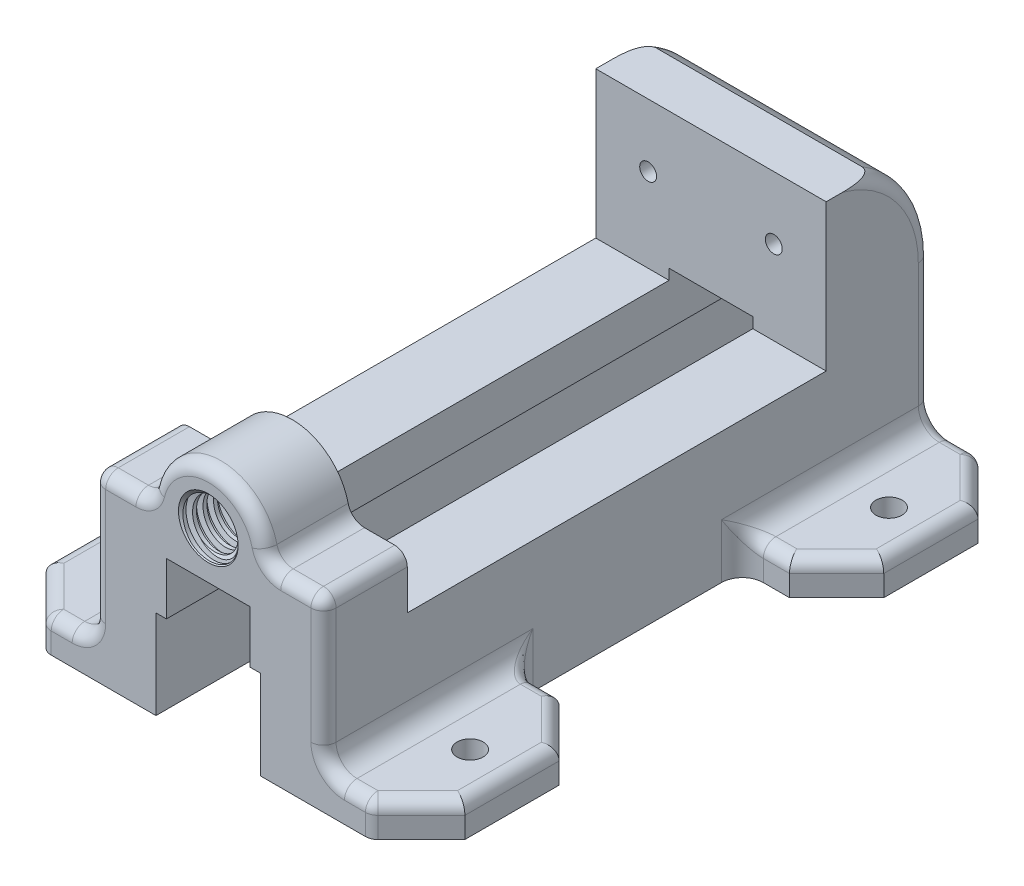
SolidWorks part; units mm, degrees
ref_plane "Front Plane" through (0, 0, 0) normal (0, 0, 1) x (1, 0, 0)
ref_plane "Top Plane" through (0, 0, 0) normal (0, 1, 0) x (1, 0, 0)
ref_plane "Right Plane" through (0, 0, 0) normal (1, 0, 0) x (0, 0, -1)
sketch "Sketch2" plane through (0, 0, 0) normal (0, 0, 1) x (1, 0, 0)
  line L1 (-34.925, 0) -> (34.925, 0)
  line L2 (-34.925, 0) -> (-34.925, 39.6748)
  line L3 (-34.925, 39.6748) -> (34.925, 39.6748)
  line L4 (34.925, 0) -> (34.925, 39.6748)
  dimension "D1" = 69.85
  dimension "D2" = 39.6748
extrude "Boss-Extrude1" add sketch "Sketch2" along normal mid plane 184.15
sketch "Sketch3" plane through (-34.925, 0, 0) normal (-1, 0, 0) x (0, 0, 1)
  line L0 (-92.075, 39.6748) -> (-60.325, 39.6748)
  line L1 (92.075, 39.6748) -> (-92.075, 39.6748) construction
  line L2 (-60.325, 39.6748) -> (-60.325, 84.1248)
  line L3 (-60.325, 84.1248) -> (-74.9527, 84.1248)
  line L4 (-92.075, 54.0779) -> (-92.075, 39.6748)
  arc A0 (-74.9527, 84.1248) -> (-92.075, 54.0779) centre (-57.15, 54.0779) ccw
  dimension "D3" = 34.925
  dimension "D1" = 31.75
  dimension "D2" = 44.45
extrude "Boss-Extrude2" add sketch "Sketch3" against normal up to surface (69.85 mm away) up to face at (34.925, 19.8374, 0)
sketch "Sketch4" plane through (0, 0, 92.075) normal (0, 0, 1) x (1, 0, 0)
  line L0 (0, 0) -> (0, 57.15) construction
  line L1 (34.925, 39.6748) -> (34.925, 55.5498)
  line L2 (34.925, 84.1248) -> (34.925, 39.6748) construction
  line L3 (34.925, 55.5498) -> (17.4498, 55.5498)
  line L4 (-17.4498, 55.5498) -> (-34.925, 55.5498)
  line L5 (-34.925, 39.6748) -> (-34.925, 84.1248) construction
  line L6 (-34.925, 55.5498) -> (-34.925, 39.6748)
  line L7 (-34.925, 39.6748) -> (34.925, 39.6748)
  arc A0 (17.4498, 55.5498) -> (-17.4498, 55.5498) centre (0, 55.5498) ccw
  dimension "D1" = 17.4498
  dimension "D2" = 55.5498
extrude "Boss-Extrude3" add sketch "Sketch4" against normal offset from surface (25.4 mm away) 127 up to face at (0, 61.8998, -60.325)
sketch "Sketch6" plane through (0, 0, 0) normal (0, -1, 0) x (1, 0, 0)
  line L0 (-49.2125, -34.925) -> (-63.5, -49.2125)
  line L1 (-34.925, -92.075) -> (-49.2125, -92.075)
  line L2 (-34.925, -92.075) -> (-34.925, -34.925)
  line L3 (-34.925, -34.925) -> (-49.2125, -34.925)
  line L4 (-63.5, -77.7875) -> (-63.5, -49.2125)
  line L5 (-49.2125, -92.075) -> (-63.5, -77.7875)
  line L6 (0, 0) -> (-25.1626, 0) construction
  line L7 (-25.1626, 0) -> (0, 0) construction
  line L8 (0, 0) -> (0, -81.2732) construction
  line L9 (-34.925, -63.5) -> (0, -63.5) construction
  circle A0 centre (-50.8, -63.5) radius 3.9624
  dimension "D1" = 7.9248
  dimension "D2" = 50.8
  dimension "D3" = 63.5
extrude "Boss-Extrude4" add sketch "Sketch6" against normal blind 10.16
mirror "Mirror4" about plane through (0, 0, 0) normal (1, 0, 0) of "Boss-Extrude4"
mirror "Mirror5" about plane through (0, 0, 0) normal (0, 0, 1) of "Boss-Extrude4", "Mirror4"
sketch "Sketch10" plane through (0, 0, 92.075) normal (0, 0, 1) x (1, 0, 0)
  line L0 (0, 0) -> (0, 42.8625) construction
  line L1 (-15.875, 0) -> (15.875, 0)
  line L2 (-49.2125, 0) -> (49.2125, 0) construction
  line L3 (15.875, 0) -> (15.875, 26.9748)
  line L4 (15.875, 26.9748) -> (12.7, 26.9748)
  line L5 (12.7, 26.9748) -> (12.7, 42.8625)
  line L6 (12.7, 42.8625) -> (-12.7, 42.8625)
  line L7 (-12.7, 42.8625) -> (-12.7, 26.9748)
  line L8 (-12.7, 26.9748) -> (-15.875, 26.9748)
  line L9 (-15.875, 26.9748) -> (-15.875, 0)
  dimension "D1" = 31.75
  dimension "D2" = 25.4
  dimension "D3" = 42.8625
  dimension "D4" = 26.9748
extrude "Cut-Extrude1" cut sketch "Sketch10" against normal through all
sketch "Sketch14" plane through (0, 0, -60.325) normal (0, 0, 1) x (1, 0, 0)
  line L0 (0, 0) -> (0, 80.9276) construction
hole_wizard "1/4-20 Tapped Hole2" positions "Sketch15" profile "Sketch16" tap size "1/4-20" standard "ANSI Inch"
sketch "Sketch15" plane through (0, 0, -60.325) normal (0, 0, 1) x (1, 0, 0)
  line L0 (0, 0) -> (0, 80.9276) construction
  line L1 (-12.7, 39.6748) -> (-34.925, 39.6748) construction
  line L2 (0, -46.2686) -> (0, 46.2686) construction
  point P0 (-19.05, 65.0748)
  point P8 (19.05, 65.0748)
  dimension "D1" = 19.05
  dimension "D2" = 25.4
sketch "Sketch16" plane through (-19.05, 65.0748, -60.325) normal (1, 0, 0) x (0, -1, 0)
  line L0 (0, 0) -> (0, 17.5358)
  line L1 (0, 17.5358) -> (2.5527, 16.002)
  line L2 (2.5527, 16.002) -> (2.5527, 0)
  line L5 (2.5527, 0) -> (0, 0)
  line L10 (0, 17.5358) -> (-2.5527, 16.002) construction
  line L11 (0, -6.35) -> (0, 107.95) construction
  dimension "Tap Drill Dia." = 5.1054
  dimension "Tap Drill Depth" = 16.002
  dimension "Drill Angle" = 118
cosmetic thread "Hole Thread2" parameters "D1"=12.7, "D2"=6.35
cosmetic thread "Hole Thread3" parameters "D1"=12.7, "D2"=6.35
sketch "Sketch18" plane through (0, 0, 92.075) normal (0, 0, 1) x (1, 0, 0)
  line L2 (-17.4498, 55.5498) -> (17.4498, 55.5498) construction
  circle A1 centre (0, 57.15) radius 7.1438
  dimension "D1" = 14.2875
  dimension "D2" = 57.15
extrude "Cut-Extrude2" cut sketch "Sketch18" against normal up to next
chamfer "Chamfer1" distance 1.905 angle 45 2 edges at (7.1438, 57.15, 66.675) (7.1438, 57.15, 92.075)
sketch "Sketch19" plane through (0, 0, 92.075) normal (0, 0, 1) x (1, 0, 0)
  circle A0 centre (0, 57.15) radius 7.1438 construction
  circle A1 centre (0, 57.15) radius 7.1438
curve "Helix/Spiral1" pitch 3.175 height 102.235 radius 7.1438 centre (0, 57.15, 92.075) axis (0, 0, -1) start towards (0, 1, 0)
sketch "Sketch20" plane through (0, 0, 0) normal (1, 0, 0) x (0, 0, -1)
  line L0 (-93.671, 65.8813) -> (-92.4856, 65.8813)
  line L1 (-92.4856, 65.8813) -> (-92.075, 64.2938)
  line L2 (-92.075, 64.2938) -> (-94.0816, 64.2938)
  line L3 (-94.0816, 64.2938) -> (-93.671, 65.8813)
  line L4 (-93.0783, 65.8813) -> (-93.0783, 64.2938) construction
  dimension "D1" = 1.5875
  dimension "D2" = 2.0066
  dimension "D3" = 29
sweep "Cut-Sweep1" cut profiles "Sketch20" path "Helix/Spiral1" align with end faces yes
fillet "Fillet1" radius 5.08 2 edges at (-17.4498, 55.5498, 79.375) (17.4498, 55.5498, 79.375)
fillet "Fillet2" radius 6.35 4 edges at (-34.925, 10.16, -63.5) (34.925, 10.16, -63.5) (34.925, 10.16, 63.5) (-34.925, 10.16, 63.5)
fillet "Fillet3" radius 6.35 4 edges at (34.925, 8.255, -34.925) (34.925, 8.255, 34.925) (-34.925, 8.255, 34.925) (-34.925, 8.255, -34.925)
fillet "Fillet5" radius 3.81 5 edges at (28.4373, 55.5498, 92.075) (18.7883, 56.6533, 92.075) (-28.4373, 55.5498, 92.075) (-18.7883, 56.6533, 92.075) (0, 72.9996, 92.075)
fillet "Fillet6" radius 3.81 10 edges at (-34.925, 55.5498, 77.47) (-34.925, 54.4339, 90.9591) (-45.2437, 10.16, 92.075) (-36.7849, 12.0199, 92.075) (45.2437, 10.16, 92.075) (36.7849, 12.0199, 92.075) (34.925, 55.5498, 77.47) (34.925, 54.4339, 90.9591) (-34.925, 34.1249, 92.075) (34.925, 34.1249, 92.075)
fillet "Fillet7" radius 3.81 8 edges at (-34.925, 71.3694, -87.494) (-45.2437, 10.16, -92.075) (-36.7849, 12.0199, -92.075) (45.2437, 10.16, -92.075) (36.7849, 12.0199, -92.075) (34.925, 71.3694, -87.494) (-34.925, 35.2939, -92.075) (34.925, 35.2939, -92.075)
fillet "Fillet8" radius 3.81 28 edges at (-49.2125, 3.175, -92.075) (-50.3284, 9.0441, -90.9591) (-45.2437, 10.16, -34.925) (-45.2437, 10.16, 34.925) (-58.2613, 10.16, 83.0263) (-50.3284, 9.0441, 90.9591) (49.2125, 3.175, -92.075) (50.3284, 9.0441, -90.9591) (36.7849, 12.0199, -33.0651) (36.7849, 12.0199, 33.0651) (49.2125, 3.175, 92.075) (50.3284, 9.0441, 90.9591) (-58.2613, 10.16, -83.0263) (-63.5, 10.16, -63.5) (-56.3562, 10.16, -42.0688) (-36.7849, 12.0199, -33.0651) (-36.7849, 12.0199, 33.0651) (-56.3562, 10.16, 42.0688) (-63.5, 10.16, 63.5) (-49.2125, 3.175, 92.075) (58.2613, 10.16, -83.0263) (63.5, 10.16, -63.5) (56.3562, 10.16, -42.0688) (45.2437, 10.16, -34.925) (45.2437, 10.16, 34.925) (56.3562, 10.16, 42.0688) (63.5, 10.16, 63.5) (58.2613, 10.16, 83.0263)
